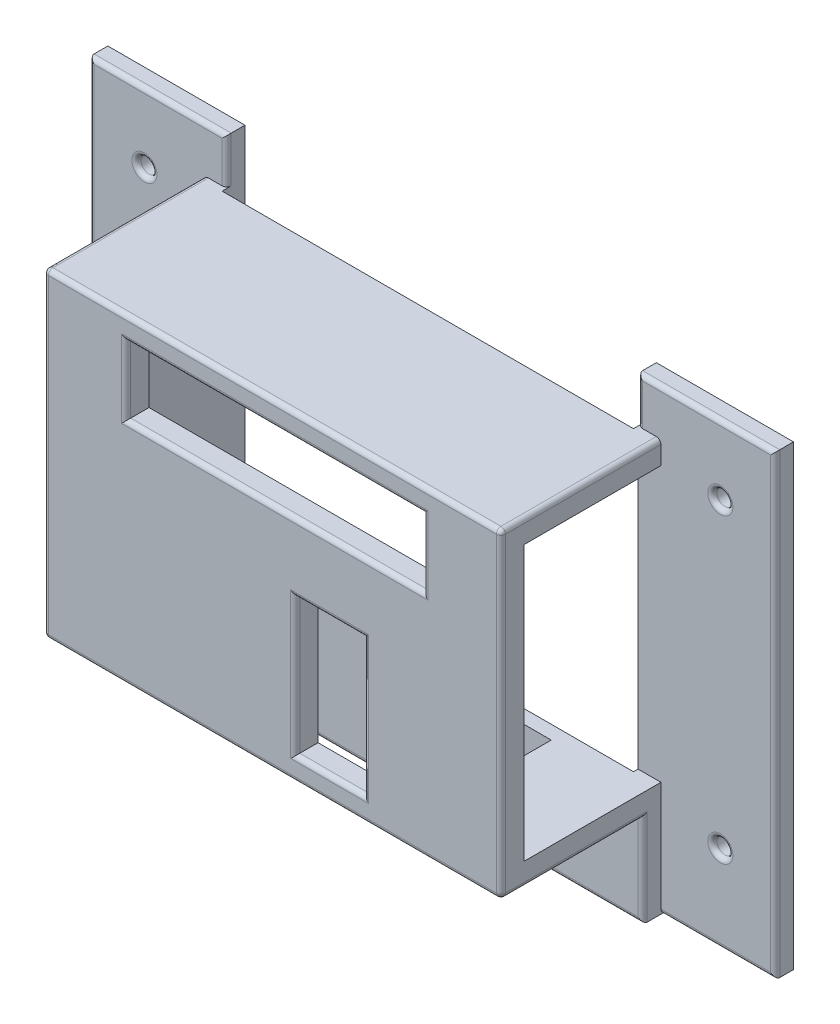
SolidWorks part; units mm, degrees
ref_plane "Front Plane" through (0, 0, 0) normal (0, 0, 1) x (1, 0, 0)
ref_plane "Top Plane" through (0, 0, 0) normal (0, 1, 0) x (1, 0, 0)
ref_plane "Right Plane" through (0, 0, 0) normal (1, 0, 0) x (0, 0, -1)
sketch "Sketch1" plane through (0, 0, 0) normal (0, 0, 1) x (1, 0, 0)
  line L1 (0, 0) -> (150, 0)
  line L2 (0, 0) -> (0, 100)
  line L3 (0, 100) -> (150, 100)
  line L4 (150, 0) -> (150, 100)
  dimension "D1" = 150
  dimension "D2" = 100
extrude "Boss-Extrude1" add sketch "Sketch1" along normal blind 4 contours L2 L1 L4 L3
sketch "Sketch2" plane through (0, 0, 4) normal (0, 0, 1) x (1, 0, 0)
  line L0 (0, 0) -> (150, 0) construction
  line L1 (125, 0) -> (25, 0)
  line L2 (125, 0) -> (125, 100)
  line L3 (125, 100) -> (25, 100)
  line L4 (25, 0) -> (25, 100)
  line L5 (0, 100) -> (150, 100) construction
  line L6 (150, 0) -> (150, 100) construction
  line L7 (0, 0) -> (0, 100) construction
  dimension "D1" = 25
  dimension "D2" = 25
extrude "Boss-Extrude2" add sketch "Sketch2" along normal blind 35
sketch "Sketch3" plane through (0, 0, 0) normal (0, -1, 0) x (-1, 0, 0)
  line L0 (-125, -39) -> (-125, -4) construction
  line L1 (-25, -39) -> (-125, -39)
  line L2 (-25, -39) -> (-25, -8)
  line L3 (-25, -8) -> (-125, -8)
  line L4 (-125, -39) -> (-125, -8)
  dimension "D1" = 31
extrude "Cut-Extrude1" cut sketch "Sketch3" against normal blind 20
sketch "Sketch4" plane through (0, 100, 0) normal (0, 1, 0) x (1, 0, 0)
  line L1 (125, -4) -> (25, -4)
  line L2 (125, -4) -> (125, -39)
  line L3 (125, -39) -> (25, -39)
  line L4 (25, -4) -> (25, -39)
extrude "Cut-Extrude2" cut sketch "Sketch4" against normal blind 10
sketch "Sketch5" plane through (125, 0, 0) normal (1, 0, 0) x (0, 0, -1)
  line L0 (-39, 20) -> (-39, 90) construction
  line L1 (-34, 25) -> (-4, 25)
  line L2 (-34, 25) -> (-34, 85)
  line L3 (-34, 85) -> (-4, 85)
  line L4 (-4, 25) -> (-4, 85)
  line L5 (-8, 20) -> (-39, 20) construction
  line L6 (-39, 90) -> (-4, 90) construction
  line L7 (-4, 0) -> (-4, 90) construction
  dimension "D1" = 5
  dimension "D2" = 5
  dimension "D3" = 5
  dimension "D4" = 0
extrude "Cut-Extrude3" cut sketch "Sketch5" against normal blind 95
sketch "Sketch6" plane through (0, 0, 0) normal (0, -1, 0) x (-1, 0, 0)
  line L0 (0, 0) -> (-150, 0) construction
  line L1 (-30, 0) -> (-120, 0)
  line L2 (-30, 0) -> (-30, -5)
  line L3 (-30, -5) -> (-120, -5)
  line L4 (-120, 0) -> (-120, -5)
  line L5 (-25, -8) -> (-25, -4) construction
  line L6 (-125, -8) -> (-125, -4) construction
  dimension "D1" = 5
  dimension "D2" = 5
  dimension "D3" = 5
extrude "Cut-Extrude4" cut sketch "Sketch6" against normal through all
sketch "Sketch7" plane through (0, 20, 0) normal (0, -1, 0) x (-1, 0, 0)
  line L0 (-25, -8) -> (-125, -8) construction
  line L1 (-30, -34) -> (-105, -34)
  line L2 (-30, -34) -> (-30, -8)
  line L3 (-30, -8) -> (-105, -8)
  line L4 (-105, -34) -> (-105, -8)
  line L5 (-25, -39) -> (-25, -8) construction
  line L6 (-125, -39) -> (-25, -39) construction
  dimension "D1" = 5
  dimension "D2" = 5
  dimension "D3" = 75
extrude "Cut-Extrude5" cut sketch "Sketch7" against normal blind 5
sketch "Sketch8" plane through (0, 0, 39) normal (0, 0, 1) x (1, 0, 0)
  line L0 (25, 90) -> (25, 20) construction
  line L1 (43, 85) -> (108, 85)
  line L2 (43, 85) -> (43, 70)
  line L3 (43, 70) -> (108, 70)
  line L4 (108, 85) -> (108, 70)
  line L5 (25, 90) -> (125, 90) construction
  dimension "D1" = 18
  dimension "D2" = 65
  dimension "D3" = 15
  dimension "D4" = 5
extrude "Cut-Extrude6" cut sketch "Sketch8" against normal blind 5
sketch "Sketch9" plane through (0, 0, 39) normal (0, 0, 1) x (1, 0, 0)
  line L0 (0, 0) -> (0, 100) construction
  line L1 (80, 55) -> (95, 55)
  line L2 (80, 55) -> (80, 25)
  line L3 (80, 25) -> (95, 25)
  line L4 (95, 55) -> (95, 25)
  line L5 (125, 20) -> (25, 20) construction
  dimension "D1" = 80
  dimension "D2" = 15
  dimension "D3" = 30
  dimension "D4" = 5
extrude "Cut-Extrude7" cut sketch "Sketch9" against normal blind 5
sketch "Sketch10" plane through (0, 0, 4) normal (0, 0, 1) x (1, 0, 0)
  line L0 (0, 0) -> (0, 100) construction
  line L1 (150, 0) -> (150, 100) construction
  line L2 (0, 100) -> (30, 100) construction
  line L3 (120, 100) -> (150, 100) construction
  line L4 (125, 0) -> (150, 0) construction
  line L5 (0, 0) -> (25, 0) construction
  circle A0 centre (12, 85) radius 1.75
  circle A1 centre (12, 19) radius 1.75
  circle A2 centre (138, 85) radius 1.75
  circle A3 centre (138, 19) radius 1.75
  dimension "D1" = 3.5
  dimension "D2" = 12
  dimension "D3" = 12
  dimension "D4" = 12
  dimension "D5" = 12
  dimension "D6" = 15
  dimension "D7" = 15
  dimension "D8" = 3.5
  dimension "D9" = 3.5
  dimension "D10" = 19
  dimension "D11" = 19
  dimension "D12" = 3.5
extrude "Cut-Extrude8" cut sketch "Sketch10" against normal blind 5
fillet "Fillet1" radius 1 4 edges at (13.75, 19, 4) (139.75, 85, 4) (139.75, 19, 4) (13.75, 85, 4)
fillet "Fillet2" radius 1 12 edges at (125, 55, 39) (75, 20, 39) (25, 55, 39) (75, 90, 39) (75.5, 70, 39) (108, 77.5, 39) (75.5, 85, 39) (43, 77.5, 39) (87.5, 25, 39) (95, 40, 39) (87.5, 55, 39) (80, 40, 39)
fillet "Fillet3" radius 1 11 edges at (124.7071, 89.7071, 38.7071) (124.7071, 20.2929, 38.7071) (25.2929, 20.2929, 38.7071) (25.2929, 89.7071, 38.7071) (125, 90, 21) (125, 10, 8) (125, 20, 23) (25, 20, 23) (25, 10, 8) (75, 0, 8) (25, 90, 21)
fillet "Fillet4" radius 1 8 edges at (12.5, 0, 4) (137.5, 0, 4) (0, 50, 4) (15, 100, 4) (135, 100, 4) (30, 95, 4) (120, 95, 4) (150, 50, 4)
fillet "Fillet5" radius 1 3 edges at (30, 20, 21) (105, 20, 21) (67.5, 20, 34)
